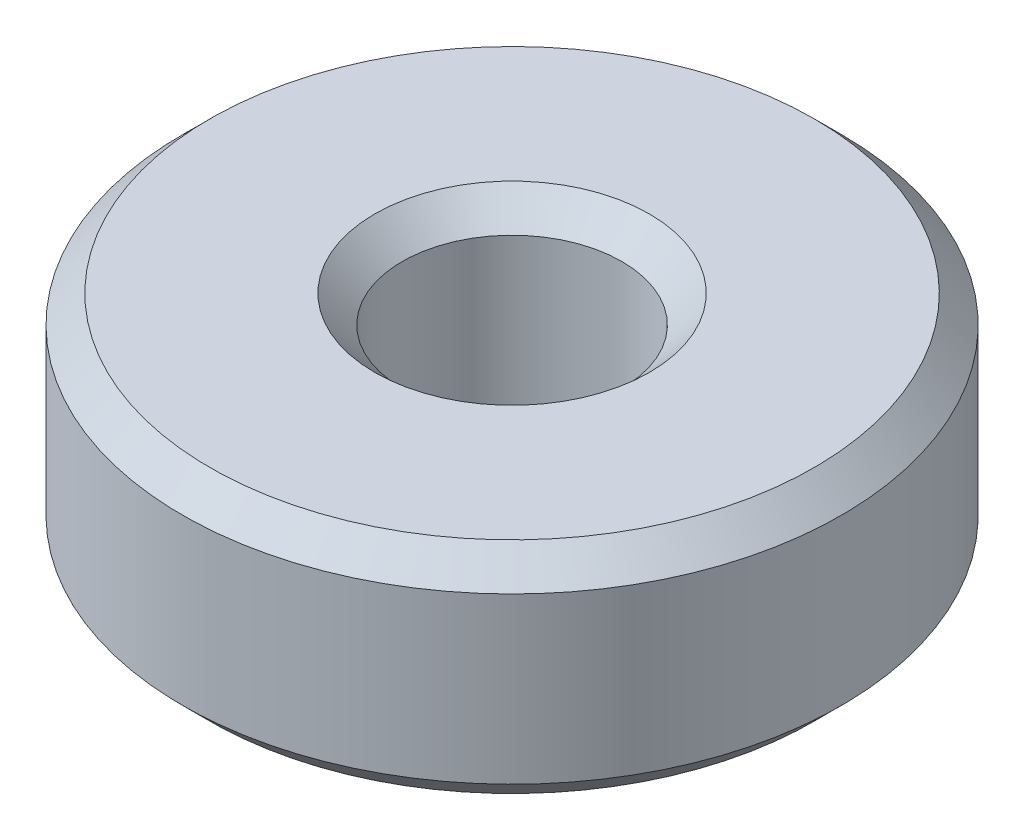
SolidWorks part; units mm, degrees
ref_plane "Front Plane" through (0, 0, 0) normal (0, 0, 1) x (1, 0, 0)
ref_plane "Top Plane" through (0, 0, 0) normal (0, 1, 0) x (1, 0, 0)
ref_plane "Right Plane" through (0, 0, 0) normal (1, 0, 0) x (0, 0, -1)
sketch "Sketch2" plane through (0, 0, 0) normal (0, 0, 1) x (1, 0, 0)
  line L0 (0, 0) -> (0, 4) construction
  line L1 (2.5, 0) -> (5.5, 0)
  line L2 (5.5, 0) -> (6, 0.5)
  line L3 (6, 0.5) -> (6, 3.5)
  line L4 (6, 3.5) -> (5.5, 4)
  line L5 (5.5, 4) -> (2.5, 4)
  line L6 (2.5, 4) -> (2, 3.5)
  line L7 (2, 3.5) -> (2, 0.5)
  line L8 (2, 0.5) -> (2.5, 0)
  point P11 (0, 0)
  point P12 (-2.8152, 11.7072)
  point P13 (6, 5.6836)
  point P14 (1.6811, 3.7232)
  point P15 (3.3965, 0)
  point P16 (4.3767, 0)
  point P17 (0, 0)
  point P18 (0, 0)
  point P19 (4.2128, 6.7105)
  point P20 (2.7299, 4)
  dimension "D1" = 12
  dimension "D2" = 4
  dimension "D3" = 4
  dimension "D4" = 0.5
revolve "Revolve1" add sketch "Sketch2" angle 360 about L0
